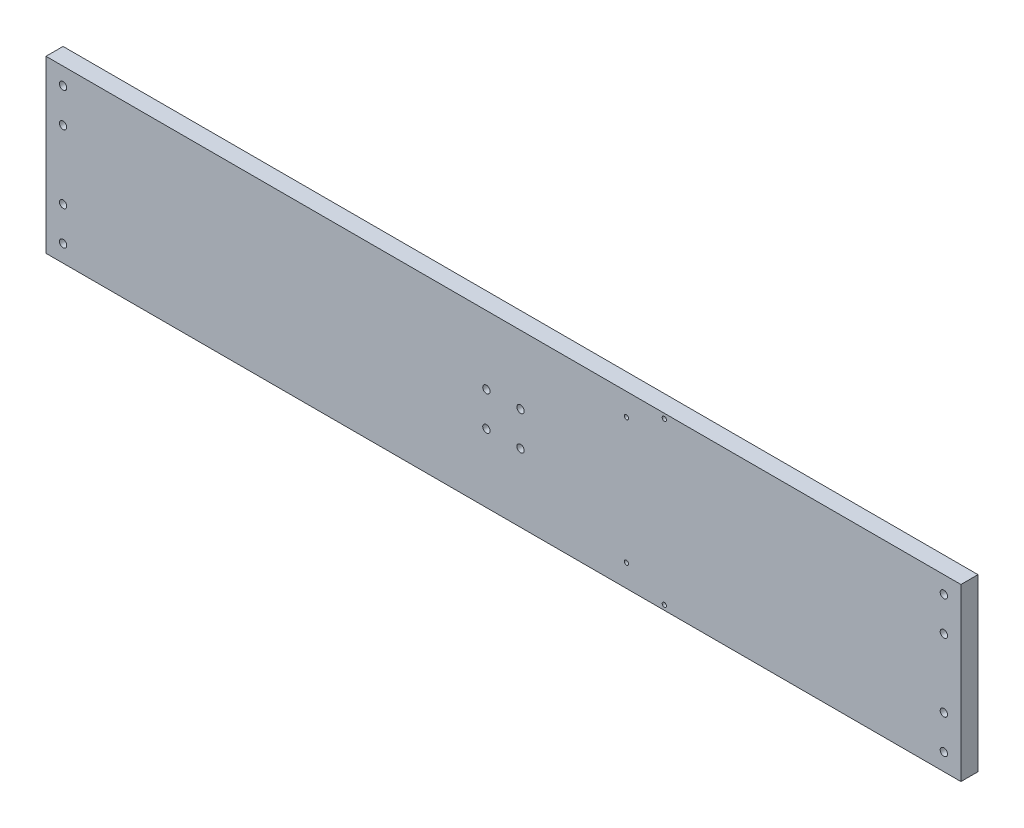
SolidWorks part; units mm, degrees
ref_plane "Piano frontale" through (0, 0, 0) normal (0, 0, 1) x (1, 0, 0)
ref_plane "Piano superiore" through (0, 0, 0) normal (0, 1, 0) x (1, 0, 0)
ref_plane "Piano destro" through (0, 0, 0) normal (1, 0, 0) x (0, 0, -1)
sketch "Schizzo1" plane through (0, 0, 0) normal (0, 0, 1) x (1, 0, 0)
  line L0 (10, 100) -> (10, 0) construction
  line L1 (0, 0) -> (536, 0)
  line L2 (0, 0) -> (0, 100)
  line L3 (0, 100) -> (536, 100)
  line L4 (536, 0) -> (536, 100)
  line L5 (0, 50) -> (10.4526, 50) construction
  line L6 (268, 100) -> (268, 0) construction
  line L7 (536, 50) -> (525.5474, 50) construction
  line L8 (526, 100) -> (526, 0) construction
  circle A0 centre (10, 90) radius 2.15
  circle A1 centre (10, 70) radius 2.15
  circle A2 centre (10, 30) radius 2.15
  circle A3 centre (526, 10) radius 2.15
  circle A4 centre (526, 30) radius 2.15
  circle A5 centre (526, 70) radius 2.15
  circle A6 centre (10, 10) radius 2.15
  circle A7 centre (526, 90) radius 2.15
  dimension "D4" = 4.3
  dimension "D5" = 10
  dimension "D1" = 100
  dimension "D2" = 536
  dimension "D3" = 40
  dimension "D6" = 20
extrude "Estrusione-Estrusione1" add sketch "Schizzo1" against normal blind 10
sketch "Schizzo2" plane through (0, 0, 0) normal (0, 0, 1) x (1, 0, 0)
  line L0 (268, 100) -> (268, 0) construction
  line L1 (536, 100) -> (0, 100) construction
  line L2 (0, 50) -> (536, 50) construction
  line L3 (0, 0) -> (536, 0) construction
  line L4 (285, 50) -> (265, 50) construction
  line L9 (0, 100) -> (0, 0) construction
  line L10 (536, 0) -> (536, 100) construction
  circle A0 centre (258, 60) radius 2.15
  circle A1 centre (278, 60) radius 2.15
  circle A4 centre (278, 40) radius 2.15
  circle A5 centre (258, 40) radius 2.15
  dimension "D3" = 4.3
  dimension "D1" = 10
  dimension "D2" = 10
  dimension "D4" = 10
extrude "Taglio-Estrusione1" cut sketch "Schizzo2" against normal through all
sketch "Sketch1" plane through (0, 0, 0) normal (0, 0, 1) x (1, 0, 0)
  point P0 (340.0471, 86.9)
  point P1 (362.2471, 97.2)
  point P3 (340.0471, 13.1)
  point P5 (362.2471, 2.8)
hole_wizard "M3 Tapped Hole1" positions "3DSketch1" profile "Sketch2" tap size "M3" standard "ISO"
sketch3d "3DSketch1"
  point P0 (362.2471, 97.2, 0)
  point P3 (340.0471, 86.9, 0)
  point P6 (340.0471, 13.1, 0)
  point P9 (362.2471, 2.8, 0)
sketch "Sketch2" plane through (362.2471, 97.2, 0) normal (1, 0, 0) x (0, -1, 0)
  line L0 (0, 0) -> (0, 12.2511)
  line L1 (0, 12.2511) -> (1.25, 11.5)
  line L2 (1.25, 11.5) -> (1.25, 0)
  line L5 (1.25, 0) -> (0, 0)
  line L10 (0, 12.2511) -> (-1.25, 11.5) construction
  line L11 (0, -6.35) -> (0, 107.95) construction
  dimension "Tap Drill Dia." = 2.5
  dimension "Tap Drill Depth" = 11.5
  dimension "Drill Angle" = 118
